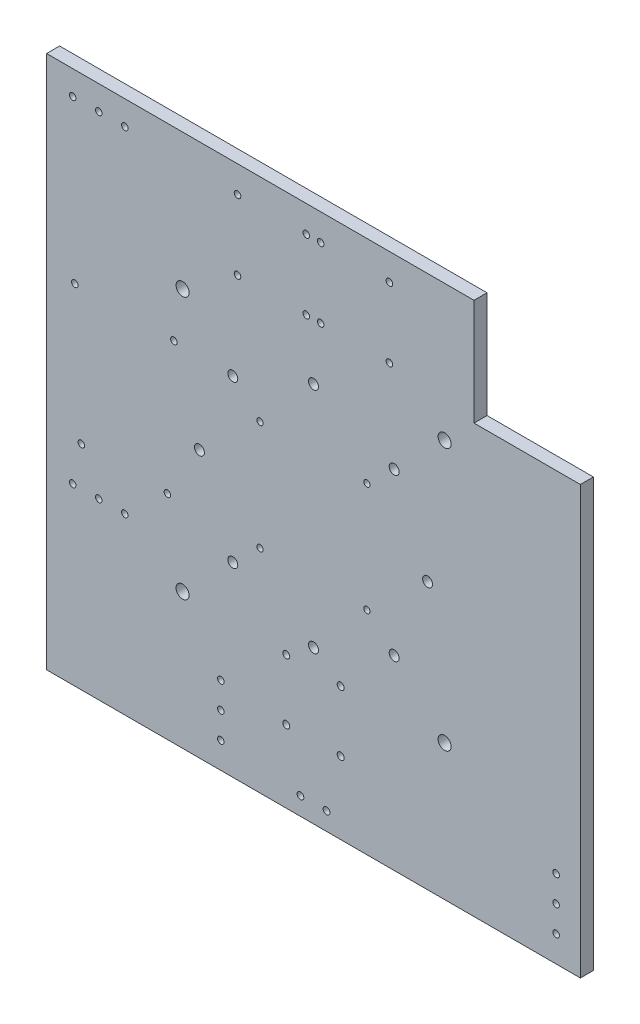
SolidWorks part; units mm, degrees
material "Perspex (TM) GS Acrylic Cast Sheet"
ref_plane "Front Plane" through (0, 0, 0) normal (0, 0, 1) x (1, 0, 0)
ref_plane "Top Plane" through (0, 0, 0) normal (0, 1, 0) x (1, 0, 0)
ref_plane "Right Plane" through (0, 0, 0) normal (1, 0, 0) x (0, 0, -1)
sketch "Sketch1" plane through (0, 0, 0) normal (0, 0, 1) x (1, 0, 0)
  line L0 (-130, 130) -> (130, 130)
  line L1 (130, 130) -> (130, -130)
  line L2 (130, -130) -> (-130, -130)
  line L3 (-130, -130) -> (-130, 130)
  line L4 (-119.4277, 48.0736) -> (-119.4277, -19.2367)
  line L5 (-29, 8) -> (-29, -8)
  line L6 (-29, 8) -> (-26.035, 8)
  line L7 (-26.035, 8) -> (-26.035, -8)
  line L8 (32.385, 33.02) -> (-32.385, 33.02)
  line L9 (-26.035, -8) -> (-29, -8)
  line L10 (-32.385, 33.02) -> (-32.385, -33.02)
  line L11 (-32.385, -33.02) -> (32.385, -33.02)
  line L12 (32.385, -33.02) -> (32.385, 33.02)
  line L13 (-106.7259, -31.9385) -> (-77.353, -31.9385)
  line L14 (-113.0777, 54.4236) -> (-71.0036, 54.4236)
  line L15 (-78.8426, 54.4236) -> (-78.8426, 37.413)
  line L16 (-64.6536, -19.2391) -> (-64.6536, 48.0736)
  line L17 (-78.8426, 37.413) -> (-94.3252, 37.413)
  line L18 (-40, 120) -> (40, 120)
  line L19 (-94.3252, 37.413) -> (-94.3252, 54.4236)
  line L31 (-40, 120) -> (-40, 80)
  line L32 (-40, 80) -> (40, 80)
  line L33 (40, 80) -> (40, 120)
  line L34 (-35, 100) -> (-35, 114.5)
  line L35 (-35, 114.5) -> (-29, 114.5)
  line L36 (-29, 114.5) -> (-29, 85.5)
  line L37 (-29, 85.5) -> (-35, 85.5)
  line L38 (-35, 85.5) -> (-35, 100)
  line L46 (16.75, -63) -> (16.75, -97)
  line L49 (16.75, -97) -> (-16.75, -97)
  line L50 (-16.75, -97) -> (-16.75, -63)
  line L51 (-16.75, -63) -> (16.75, -63)
  line L56 (120, 41.2) -> (120, -41.2)
  line L57 (45, 41.2) -> (45, -41.2)
  line L58 (120, 41.2) -> (45, 41.2)
  line L60 (45, -41.2) -> (120, -41.2)
  circle A0 centre (-26.035, 26.67) radius 1.55
  circle A1 centre (-26.035, -26.67) radius 1.55
  circle A2 centre (26.035, 26.67) radius 1.55
  circle A3 centre (26.035, -26.67) radius 1.55
  circle A4 centre (-116.2527, 39.8165) radius 1.5875
  circle A5 centre (-113.0777, -26.2214) radius 1.5875
  arc A6 (-119.4277, -19.2367) -> (-106.7259, -31.9385) centre (-106.7259, -19.2367) ccw
  arc A7 (-77.353, -31.9385) -> (-64.6536, -19.2391) centre (-77.353, -19.2391) ccw
  arc A8 (-113.0777, 54.4236) -> (-119.4277, 48.0736) centre (-113.0777, 48.0736) ccw
  arc A9 (-64.6536, 48.0736) -> (-71.0036, 54.4236) centre (-71.0036, 48.0736) ccw
  circle A10 centre (-67.9927, 39.8186) radius 1.5875
  circle A11 centre (-37, 117) radius 1.6
  circle A12 centre (-37, 83) radius 1.6
  circle A13 centre (-3.5, 117) radius 1.6
  circle A14 centre (-3.5, 83) radius 1.6
  circle A15 centre (3.5, 117) radius 1.6
  circle A16 centre (37, 117) radius 1.6
  circle A17 centre (37, 83) radius 1.6
  circle A18 centre (3.5, 83) radius 1.6
  circle A19 centre (-13.25, -65.25) radius 1.7
  circle A20 centre (13.25, -65.25) radius 1.7
  circle A21 centre (13.25, -94.75) radius 1.7
  circle A22 centre (-13.25, -94.75) radius 1.7
  circle A23 centre (-76.1972, 90.422) radius 3.175
  circle A24 centre (0, 55.575) radius 2.415
  circle A25 centre (-55.575, 0) radius 2.415
  circle A26 centre (0, -55.575) radius 2.415
  circle A27 centre (55.575, 0) radius 2.415
  circle A28 centre (-39.2975, 39.2975) radius 2.415
  circle A29 centre (39.2975, 39.2975) radius 2.415
  circle A30 centre (39.2975, -39.2975) radius 2.415
  circle A31 centre (-39.2975, -39.2975) radius 2.415
  circle A32 centre (76.33, 76.33) radius 3.175
  circle A33 centre (76.33, -76.33) radius 3.175
  circle A34 centre (-76.33, -76.33) radius 3.175
  arc A35 (-2.4144, 55.5225) -> (-37.5531, 40.9676) centre (0, 0) ccw
  arc A36 (37.5531, 40.9676) -> (2.4144, 55.5225) centre (0, 0) ccw
  arc A37 (55.5225, 2.4144) -> (40.9676, 37.5531) centre (0, 0) ccw
  arc A38 (40.9676, -37.5531) -> (55.5225, -2.4144) centre (0, 0) ccw
  arc A39 (2.4144, -55.5225) -> (37.5531, -40.9676) centre (0, 0) ccw
  arc A40 (-37.5531, -40.9676) -> (-2.4144, -55.5225) centre (0, 0) ccw
  arc A41 (-55.5225, -2.4144) -> (-40.9676, -37.5531) centre (0, 0) ccw
  arc A42 (-40.9676, 37.5531) -> (-55.5225, 2.4144) centre (0, 0) ccw
  circle A43 centre (-71.1677, -26.2214) radius 1.5875
  circle A44 centre (6.35, -121.3) radius 1.651
  circle A45 centre (-6.35, -121.3) radius 1.651
  circle A46 centre (121.3, 126.35) radius 1.651
  circle A47 centre (121.3, 113.65) radius 1.651
  point P127 (127.65, 120)
  point P128 (-120, -120)
  point P129 (0, -127.65)
extrude "Boss-Extrude2" add sketch "Sketch1" along normal blind 6.35 contours L0 L1 L2 L3 | A10 | A43 | A5 | A4 | A25 | A28 | A24 | A31 | A26 | A30 | A27 | A29 | A1 | A3 | A2 | A0 | A22 | A21 | A20 | A19 | A45 | A44 | A46 | A47 | A17 | A16 | A18 | A14 | A15 | A13 | A11 | A12
sketch "Sketch2" plane through (0, 0, 0) normal (0, 0, -1) x (-1, 0, 0)
  circle A0 centre (0, 0) radius 55.6086 construction
sketch "Sketch5" plane through (0, 0, 0) normal (0, 0, -1) x (-1, 0, 0)
  line L0 (-78.2, 78.2) -> (-78.2, 131)
  line L1 (-78.2, 131) -> (-131, 131)
  line L2 (-131, 131) -> (-131, 78.2)
  line L3 (-131, 78.2) -> (-78.2, 78.2)
  line L4 (-130, 130) -> (-130, 79.2)
  line L5 (-130, 79.2) -> (-79.2, 79.2)
  line L6 (-79.2, 79.2) -> (-79.2, 130)
  line L7 (-79.2, 130) -> (-130, 130)
  line L8 (-130, 130) -> (-130, 79.2)
  line L9 (-130, 79.2) -> (-79.2, 79.2)
  line L10 (-79.2, 79.2) -> (-79.2, 130)
  line L11 (-79.2, 130) -> (-130, 130)
  dimension "D1" = 0
  dimension "D2" = 1
extrude "Cut-Extrude1" cut sketch "Sketch5" against normal through all contours L2 L3 L0 L1
sketch "Sketch6" plane through (0, 0, 0) normal (0, 0, -1) x (-1, 0, 0)
  circle A0 centre (63.7786, 63.7786) radius 3.175 construction
  circle A1 centre (-63.8746, 63.7786) radius 3.175 construction
  circle A2 centre (-63.8746, -63.8746) radius 3.175 construction
  circle A3 centre (63.7786, -63.8746) radius 3.175 construction
  circle A4 centre (63.7786, 63.7786) radius 3.175
  circle A5 centre (-63.8746, 63.7786) radius 3.175
  circle A6 centre (-63.8746, -63.8746) radius 3.175
  circle A7 centre (63.7786, -63.8746) radius 3.175
extrude "Cut-Extrude2" cut sketch "Sketch6" against normal through all contours A7 | A6 | A5 | A4
sketch "Sketch7" plane through (0, 0, 0) normal (0, 0, -1) x (-1, 0, 0)
  circle A0 centre (91.9, 118.189) radius 1.5875 construction
  circle A1 centre (104.6, 118.189) radius 1.5875 construction
  circle A2 centre (117.3, 118.189) radius 1.5875 construction
  circle A3 centre (91.9, -45.133) radius 1.5875 construction
  circle A4 centre (104.6, -45.133) radius 1.5875 construction
  circle A5 centre (117.3, -45.133) radius 1.5875 construction
  circle A6 centre (45.133, -117.3) radius 1.5875 construction
  circle A7 centre (45.133, -104.6) radius 1.5875 construction
  circle A8 centre (45.133, -91.9) radius 1.5875 construction
  circle A9 centre (-118.189, -117.3) radius 1.5875 construction
  circle A10 centre (-118.189, -104.6) radius 1.5875 construction
  circle A11 centre (-118.189, -91.9) radius 1.5875 construction
  circle A12 centre (91.9, 118.189) radius 1.5875
  circle A13 centre (104.6, 118.189) radius 1.5875
  circle A14 centre (117.3, 118.189) radius 1.5875
  circle A15 centre (91.9, -45.133) radius 1.5875
  circle A16 centre (104.6, -45.133) radius 1.5875
  circle A17 centre (117.3, -45.133) radius 1.5875
  circle A18 centre (45.133, -117.3) radius 1.5875
  circle A19 centre (45.133, -104.6) radius 1.5875
  circle A20 centre (45.133, -91.9) radius 1.5875
  circle A21 centre (-118.189, -117.3) radius 1.5875
  circle A22 centre (-118.189, -104.6) radius 1.5875
  circle A23 centre (-118.189, -91.9) radius 1.5875
extrude "Cut-Extrude3" cut sketch "Sketch7" against normal through all
